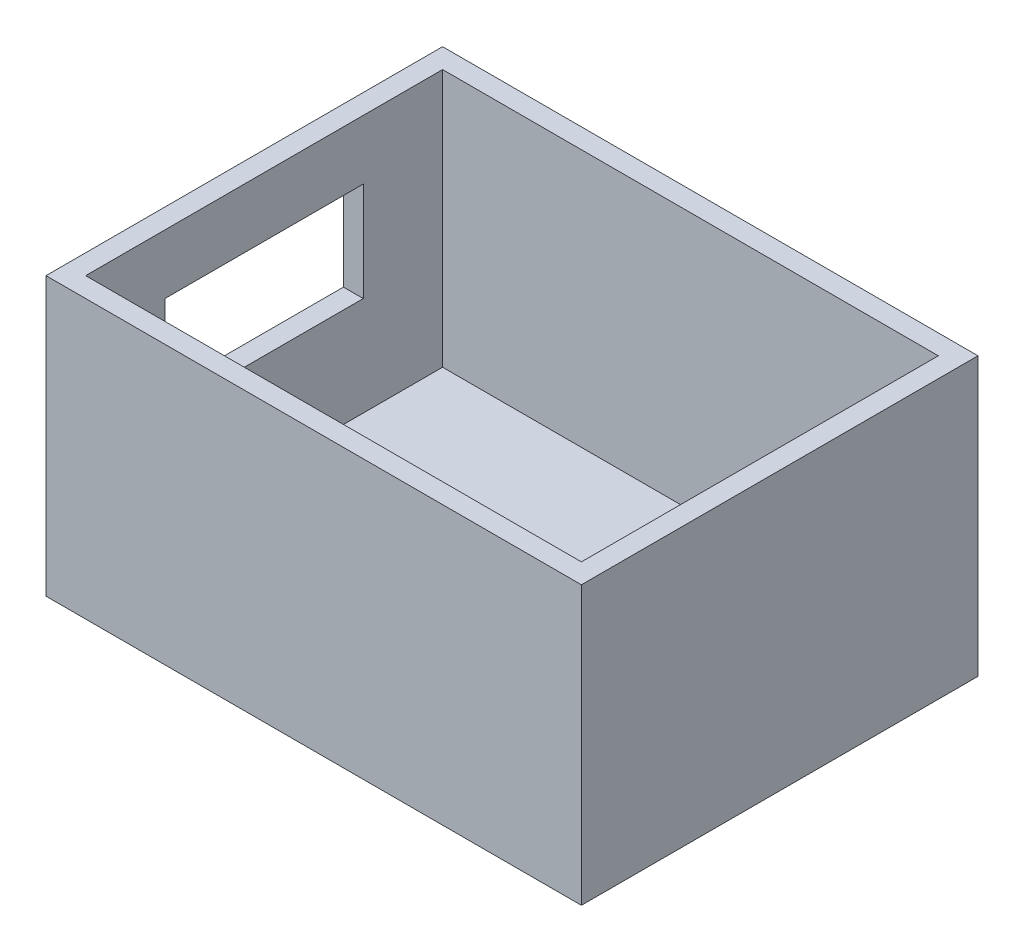
SolidWorks part; units mm, degrees
ref_plane "Alzado" through (0, 0, 0) normal (0, 0, 1) x (1, 0, 0)
ref_plane "Planta" through (0, 0, 0) normal (0, 1, 0) x (1, 0, 0)
ref_plane "Vista lateral" through (0, 0, 0) normal (1, 0, 0) x (0, 0, -1)
sketch "Croquis1" plane through (0, 0, 0) normal (0, 1, 0) x (1, 0, 0)
  line L0 (-1, -1) -> (-1, 19)
  line L1 (0, 0) -> (25, 0)
  line L2 (0, 0) -> (0, 18)
  line L3 (0, 18) -> (25, 18)
  line L4 (25, 0) -> (25, 18)
  line L5 (-1, 19) -> (26, 19)
  line L6 (26, -1) -> (26, 19)
  line L7 (-1, -1) -> (26, -1)
  dimension "D1" = 18
  dimension "D2" = 25
  dimension "D3" = 1
extrude "Saliente-Extruir1" add sketch "Croquis1" along normal blind 14 contours L2 L1 L4 L3 | L0 L5 L6 L7
extrude "Saliente-Extruir2" add sketch "Croquis1<3>" along normal blind 1 contours L1 L4 L3 L2 region at (12.5, 0, -9)
sketch "Croquis1<3>" plane through (0, 0, 0) normal (0, 1, 0) x (1, 0, 0) same geometry as "Croquis1"
sketch "Croquis2" plane through (-1, 0, 0) normal (-1, 0, 0) x (0, 0, 1)
  line L0 (-9, 14) -> (-9, 0)
  line L1 (1, 14) -> (-19, 14) construction
  line L2 (1, 0) -> (-19, 0) construction
  line L4 (-14, 11) -> (-4, 11)
  line L5 (-14, 11) -> (-14, 6)
  line L6 (-14, 6) -> (-4, 6)
  line L7 (-4, 11) -> (-4, 6)
  line L8 (-14, 11) -> (-4, 6) construction
  line L9 (-14, 6) -> (-4, 11) construction
  point P6 (-9, 8.5)
  point P11 (0, 0)
  dimension "D1" = 5
  dimension "D2" = 10
  dimension "D3" = 8.5
extrude "Cortar-Extruir1" cut sketch "Croquis2" against normal blind 1 contours L5 L6 L0 L4 | L7 L4 L0 L6 region at (-1, 8.5, -6.5) region at (-1, 8.5, -11.5)
